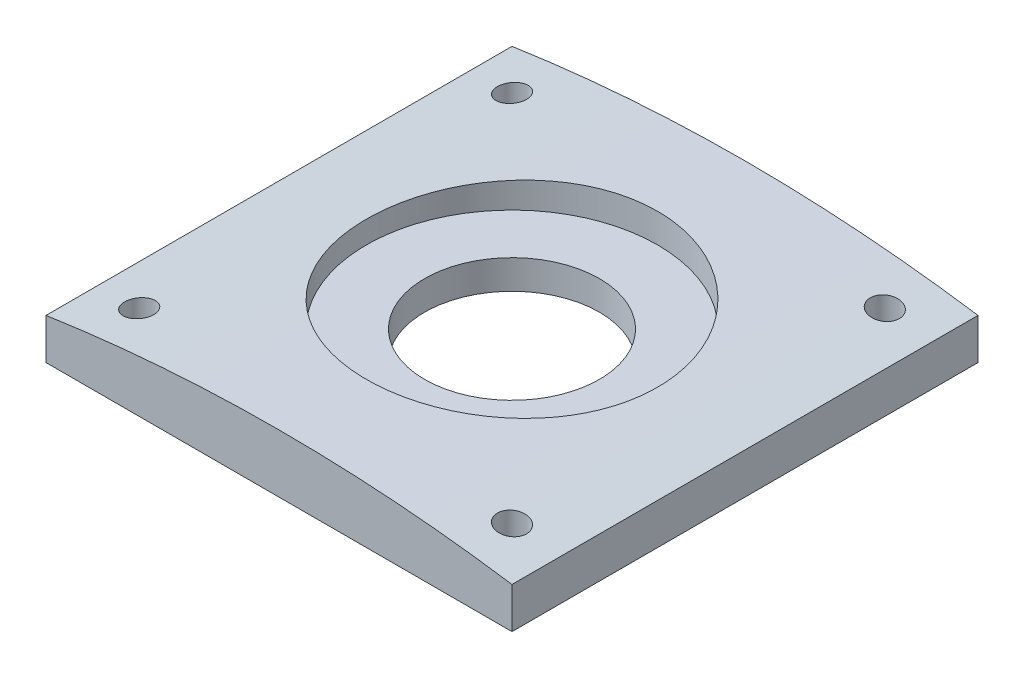
SolidWorks part; units mm, degrees
ref_plane "Front Plane" through (0, 0, 0) normal (0, 0, 1) x (1, 0, 0)
ref_plane "Top Plane" through (0, 0, 0) normal (0, 1, 0) x (1, 0, 0)
ref_plane "Right Plane" through (0, 0, 0) normal (1, 0, 0) x (0, 0, -1)
sketch "Sketch1" plane through (0, 0, 0) normal (0, 1, 0) x (1, 0, 0)
  line L1 (-40, -40) -> (40, -40)
  line L2 (-40, -40) -> (-40, 40)
  line L3 (-40, 40) -> (40, 40)
  line L4 (40, -40) -> (40, 40)
  line L5 (-40, -40) -> (40, 40) construction
  line L6 (-40, 40) -> (40, -40) construction
  circle A0 centre (0, 0) radius 15
  circle A1 centre (0, 0) radius 25
  circle A2 centre (-32, 32) radius 2.5
  circle A3 centre (-32, -32) radius 2.5
  circle A4 centre (32, -32) radius 2.5
  circle A5 centre (32, 32) radius 2.5
  point P19 (0, 0)
  dimension "D1" = 50
  dimension "D2" = 30
  dimension "D4" = 5
  dimension "D3" = 80
  dimension "D5" = 8
  dimension "D6" = 4
extrude "Boss-Extrude3" add sketch "Sketch1<3>" against normal blind 5 contours L1 L4 L3 L2 A1 | A1 A0 region at (-38.8686, 0, 0) region at (-24.2929, 0, 0)
sketch "Sketch1<3>" plane through (0, 0, 0) normal (0, 1, 0) x (1, 0, 0) same geometry as "Sketch1"
extrude "Boss-Extrude4" add sketch "Sketch1" along normal blind 5 contours L1 L4 L3 L2 A1 region at (-38.8686, 0, 0)
sketch "Sketch3" plane through (0, 0, 0) normal (0, 0, 1) x (1, 0, 0)
  line L0 (0, 5) -> (0, -265) construction
  line L1 (-40, 5) -> (40, 5) construction
  line L2 (40, -5) -> (40, 5) construction
  line L3 (-40, -5) -> (-40, 5) construction
  line L4 (-40, 2.0206) -> (-40, 5)
  line L5 (-40, 5) -> (0, 5)
  line L6 (40, 5) -> (40, 2.0206)
  line L7 (0, 5) -> (40, 5)
  arc A0 (0, 5) -> (40, 2.0206) centre (0, -265) cw
  arc A1 (0, 5) -> (-40, 2.0206) centre (0, -265) ccw
  dimension "D1" = 270
extrude "Cut-Extrude2" cut sketch "Sketch3" against normal through all both and the other way through all contours A1 L4 L5
extrude "Cut-Extrude3" cut sketch "Sketch3<4>" against normal through all both and the other way through all contours L7 L6 A0
sketch "Sketch3<4>" plane through (0, 0, 0) normal (0, 0, 1) x (1, 0, 0) same geometry as "Sketch3"
